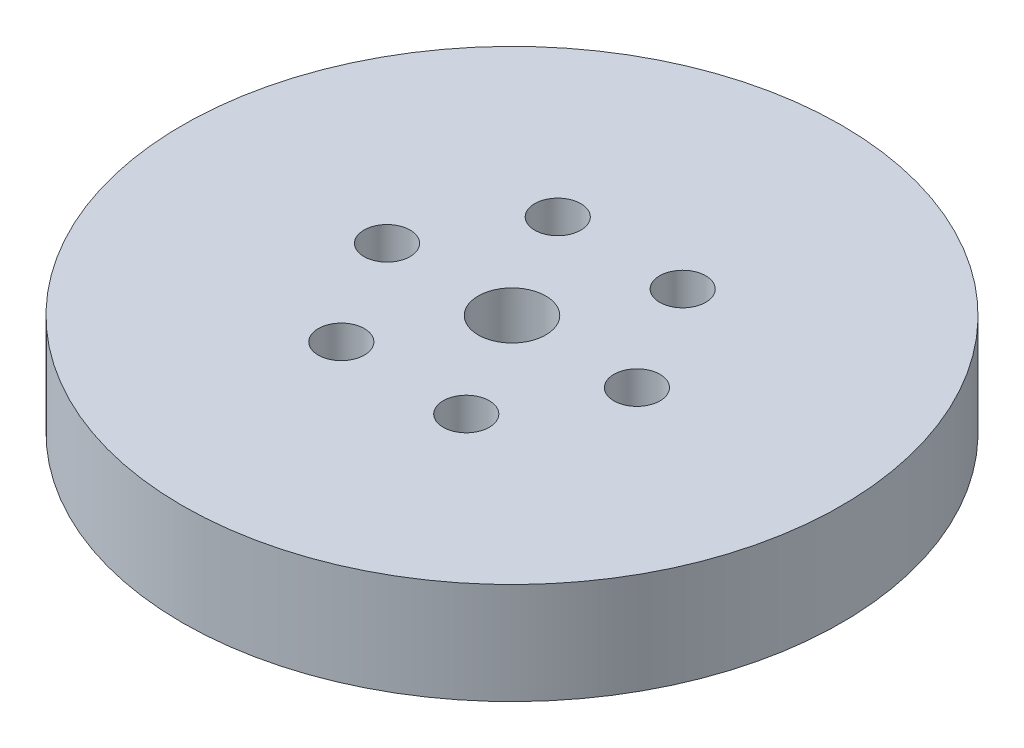
SolidWorks part; units mm, degrees
ref_plane "Front Plane" through (0, 0, 0) normal (0, 0, 1) x (1, 0, 0)
ref_plane "Top Plane" through (0, 0, 0) normal (0, 1, 0) x (1, 0, 0)
ref_plane "Right Plane" through (0, 0, 0) normal (1, 0, 0) x (0, 0, -1)
sketch "Sketch1" plane through (0, 0, 0) normal (0, 1, 0) x (1, 0, 0)
  circle A0 centre (0, 0) radius 97.5
  dimension "FLANGE_OD" = 195
extrude "Boss-Extrude1" add sketch "Sketch1" along normal blind 30
sketch "Sketch2" plane through (0, 0, 0) normal (0, 1, 0) x (1, 0, 0)
  circle A0 centre (0, 0) radius 10
  dimension "BORE_D" = 20
extrude "Cut-Extrude1" cut sketch "Sketch2" along normal through all
sketch "Sketch3" plane through (0, 30, 0) normal (0, 1, 0) x (1, 0, 0)
  circle A0 centre (0, 0) radius 36.9679 construction
  circle A1 centre (-36.9679, 0) radius 6.8191
  dimension "BOLT_D" = 13.6382
  dimension "BOLT_PCD" = 73.9358
extrude "Cut-Extrude2" cut sketch "Sketch3" against normal blind 20.1412
pattern_circular "CirPattern1" count 6 over 360 about axis through (0, 0, 0) along (0, 1, 0) of "Cut-Extrude2"
